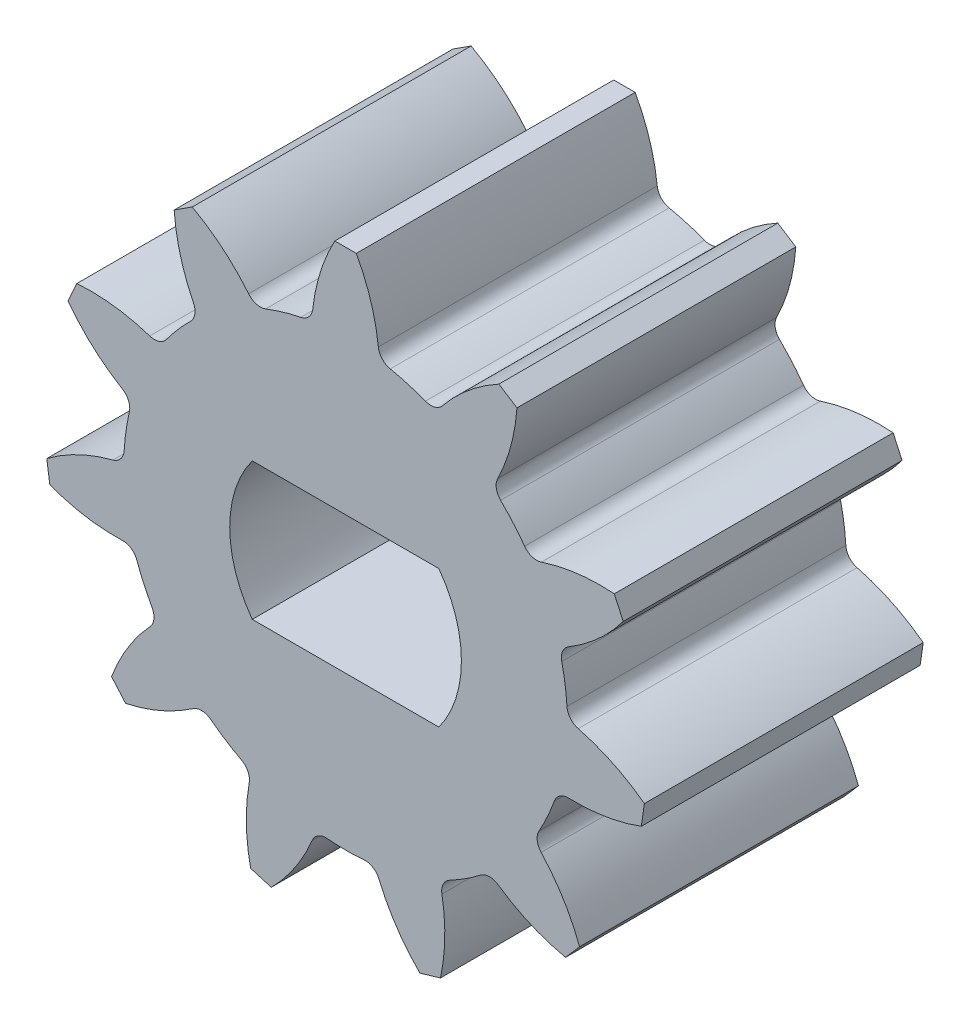
SolidWorks part; units mm, degrees
ref_plane "Plan de face" through (0, 0, 0) normal (0, 0, 1) x (1, 0, 0)
ref_plane "Plan de dessus" through (0, 0, 0) normal (0, 1, 0) x (1, 0, 0)
ref_plane "Plan de droite" through (0, 0, 0) normal (1, 0, 0) x (0, 0, -1)
sketch "Esquisse1" plane through (0, 0, 0) normal (0, 0, 1) x (1, 0, 0)
  line L0 (0, 0) -> (0, 9.0815) construction
  line L2 (2.6657, 4.4298) -> (0, 0)
  line L3 (-0.25, 7) -> (0.25, 7)
  line L4 (-0.785, 5.1101) -> (0.785, 5.1101) construction
  line L5 (-1.275, 5.0103) -> (0, 0)
  arc A0 (1.0416, 5.064) -> (2.6657, 4.4298) centre (0, 0) cw
  arc A1 (-0.25, 7) -> (-0.7642, 5.3685) centre (3.6093, 4.8868) ccw
  arc A2 (0.25, 7) -> (0.7642, 5.3685) centre (-3.6093, 4.8868) cw
  arc A3 (-0.785, 5.1101) -> (2.6657, 4.4298) centre (0, 0) ccw construction
  arc A4 (0.7642, 5.3685) -> (1.0416, 5.064) centre (1.1121, 5.4068) ccw
  arc A5 (-1.275, 5.0103) -> (-1.0416, 5.064) centre (0, 0) cw
  arc A6 (-1.0416, 5.064) -> (-0.7642, 5.3685) centre (-1.1121, 5.4068) ccw
  point P6 (0, 7)
  point P12 (-0.7557, 5.4401)
  point P13 (0.7557, 5.4401)
  point P15 (0, 5.1101)
  dimension "D5" = 4.4
  dimension "D6" = 0.33
  dimension "D1" = 5.17
  dimension "D7" = 0.35
  dimension "D10" = 0.35
  dimension "D2" = 7
  dimension "D3" = 0.5
  dimension "D4" = 1.57
  dimension "D8" = 2
  dimension "D9" = 0.5
extrude "Boss.-Extru.1" add sketch "Esquisse1" along normal blind 6.5
pattern_circular "Répétition circulaire1" count 11 over 360 about axis through (0, 0, 6.5) along (0, 0, -1) of "Boss.-Extru.1"
sketch "Esquisse2" plane through (0, 0, 6.5) normal (0, 0, 1) x (1, 0, 0)
  line L0 (-2.1749, 1.6) -> (2.1749, 1.6)
  line L1 (-2.1749, -1.6) -> (2.1749, -1.6)
  arc A0 (-2.1749, 1.6) -> (-2.1749, -1.6) centre (0, 0) ccw
  arc A1 (2.1749, -1.6) -> (2.1749, 1.6) centre (0, 0) ccw
  dimension "D1" = 5.4
  dimension "D2" = 3.2
extrude "Enlèv. mat.-Extru.1" cut sketch "Esquisse2" against normal up to next
ref_axis "Axe1" through (0, 0, 0) along (0, 0, 1)
